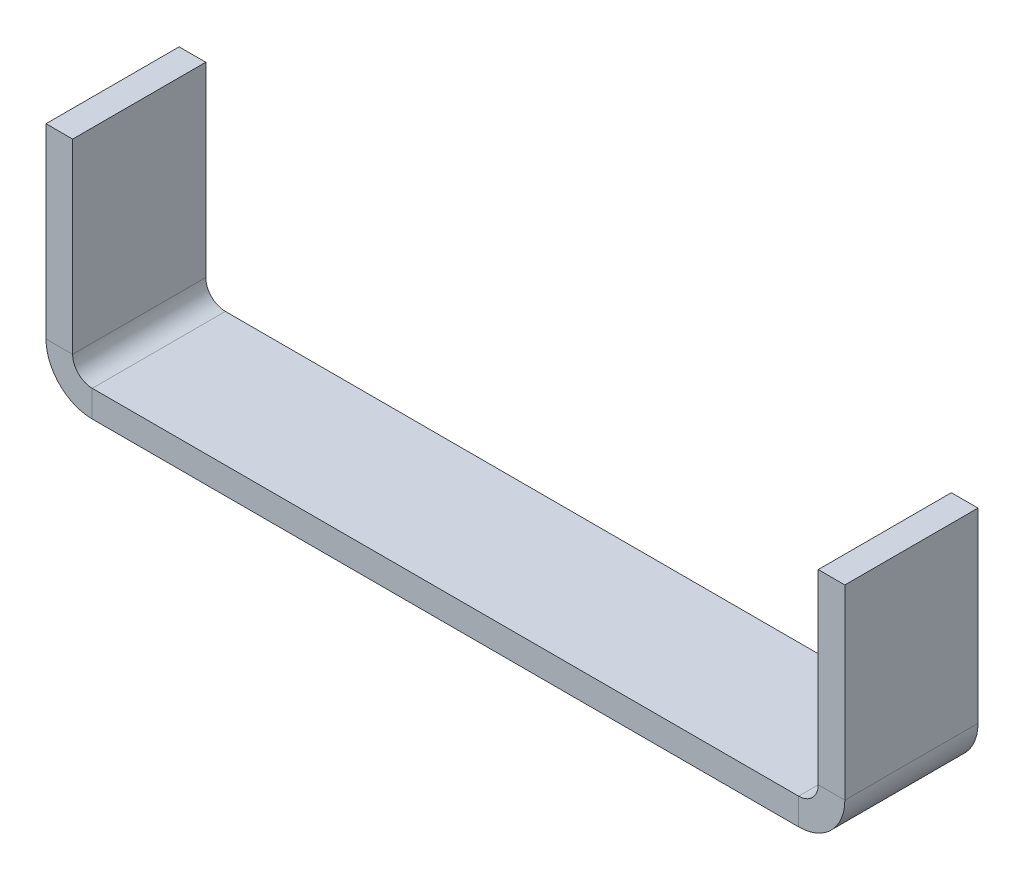
SolidWorks part; units mm, degrees
note: The reader was unsure of these and kept them because the rebuilt part matched: flange length of "Edge-Flange1", "Edge-Flange2".
ref_plane "Front Plane" through (0, 0, 0) normal (0, 0, 1) x (1, 0, 0)
ref_plane "Top Plane" through (0, 0, 0) normal (0, 1, 0) x (1, 0, 0)
ref_plane "Right Plane" through (0, 0, 0) normal (1, 0, 0) x (0, 0, -1)
sketch "Sketch1" plane through (0, 0, 0) normal (0, 1, 0) x (1, 0, 0)
  line L1 (-15, 2.5) -> (15, 2.5)
  line L2 (-15, 2.5) -> (-15, -2.5)
  line L3 (-15, -2.5) -> (15, -2.5)
  line L4 (15, 2.5) -> (15, -2.5)
  line L5 (-15, 2.5) -> (15, -2.5) construction
  line L6 (-15, -2.5) -> (15, 2.5) construction
  point P0 (0, 0)
  dimension "D1" = 30
  dimension "D2" = 5
base flange "Base-Flange1" sketch "Sketch1" thickness 1 reverse thickness direction no parameters "D1"=0.7366
ref_plane "Plane1" through (-15, 0, 2.5) normal (0, 0, 1) x (1, 0, 0)
edge flange "Edge-Flange1" sketch "Sketch9" flange angle 90 flange length 8.7366 bend radius 0.7366 thickness 1 relief rectangular parameters "D6"=10
sketch "Sketch9" plane through (-15, 0, 0) normal (-1, 0, 0) x (0, 0, 1)
  line L0 (-2.5, 0) -> (2.5, 0) construction
  line L1 (-2.5, 0) -> (2.5, 0)
  line L2 (-2.5, 0) -> (-2.5, 7.7366)
  line L3 (-2.5, 7.7366) -> (2.5, 7.7366)
  line L4 (2.5, 7.7366) -> (2.5, 0)
bend "EdgeBend1" bend radius 0.7366 bend angle 90 parameters "D5"=1
edge flange "Edge-Flange2" sketch "Sketch12" flange angle 90 flange length 8.7366 bend radius 0.7366 thickness 1 relief rectangular parameters "D6"=10
sketch "Sketch12" plane through (15, 0, 0) normal (1, 0, 0) x (0, 0, -1)
  line L0 (-2.5, 0) -> (2.5, 0) construction
  line L1 (-2.5, 0) -> (2.5, 0)
  line L2 (-2.5, 0) -> (-2.5, 7.7366)
  line L3 (-2.5, 7.7366) -> (2.5, 7.7366)
  line L4 (2.5, 7.7366) -> (2.5, 0)
bend "EdgeBend2" bend radius 0.7366 bend angle 90 parameters "D5"=2
sketch "Bend-Lines1" [suppressed] plane through (0, 0, 0) normal (0, 1, 0) x (1, 0, 0)
sketch "Bounding-Box1" [suppressed] plane through (0, 0, 0) normal (0, 1, 0) x (1, 0, 0)
sheet metal parameters "Sheet-Metal1" thickness 1 parameters "D1"=0.7366
flat pattern "Flat-Pattern1" [suppressed]
sketch "Bend-Lines2" plane through (0, 0, 0) normal (0, 1, 0) x (1, 0, 0)
sketch3d "Bounding-Box2" [suppressed]
  line L0 (-15, -2.5, 0) -> (15, -2.5, 0) construction
  line L1 (-15, 2.5, 0) -> (15, 2.5, 0) construction
  line L2 (-15, -2.5, 0) -> (-15, 2.5, 0) construction
  line L3 (15, -2.5, 0) -> (15, 2.5, 0) construction
sheet metal parameters "Sheet-Metal2" thickness 1 parameters "D1"=0.7366
flat pattern "Flat-Pattern1"
sketch "Bend-Lines2" plane through (0, 0, 0) normal (0, 1, 0) x (1, 0, 0)
  line L0 (-14.2346, 2.5) -> (-14.2346, -2.5) construction
  line L1 (-14.2346, 2.5) -> (-14.2346, -2.5) construction
sketch3d "Bounding-Box2" [suppressed]
  line L0 (15, -2.5, 0) -> (-22.2058, -2.5, 0) construction
  line L1 (15, 2.5, 0) -> (-22.2058, 2.5, 0) construction
  line L2 (15, -2.5, 0) -> (15, 2.5, 0) construction
  line L3 (-22.2058, -2.5, 0) -> (-22.2058, 2.5, 0) construction
bend of the flat pattern "Flatten-<EdgeBend1>1"
sheet metal parameters "Sheet-Metal3" thickness 1 parameters "D1"=0.7366
flat pattern "Flat-Pattern1"
sketch "Bend-Lines2" plane through (0, 0, 0) normal (0, 1, 0) x (1, 0, 0)
  line L0 (-14.2346, 2.5) -> (-14.2346, -2.5) construction
  line L1 (-14.2346, 2.5) -> (-14.2346, -2.5) construction
  line L2 (14.2346, -2.5) -> (14.2346, 2.5) construction
  line L3 (14.2346, -2.5) -> (14.2346, 2.5) construction
sketch3d "Bounding-Box2" [suppressed]
  line L0 (22.2058, -2.5, 0) -> (-22.2058, -2.5, 0) construction
  line L1 (22.2058, 2.5, 0) -> (-22.2058, 2.5, 0) construction
  line L2 (22.2058, -2.5, 0) -> (22.2058, 2.5, 0) construction
  line L3 (-22.2058, -2.5, 0) -> (-22.2058, 2.5, 0) construction
bend of the flat pattern "Flatten-<EdgeBend1>1"
bend of the flat pattern "Flatten-<EdgeBend2>1"
